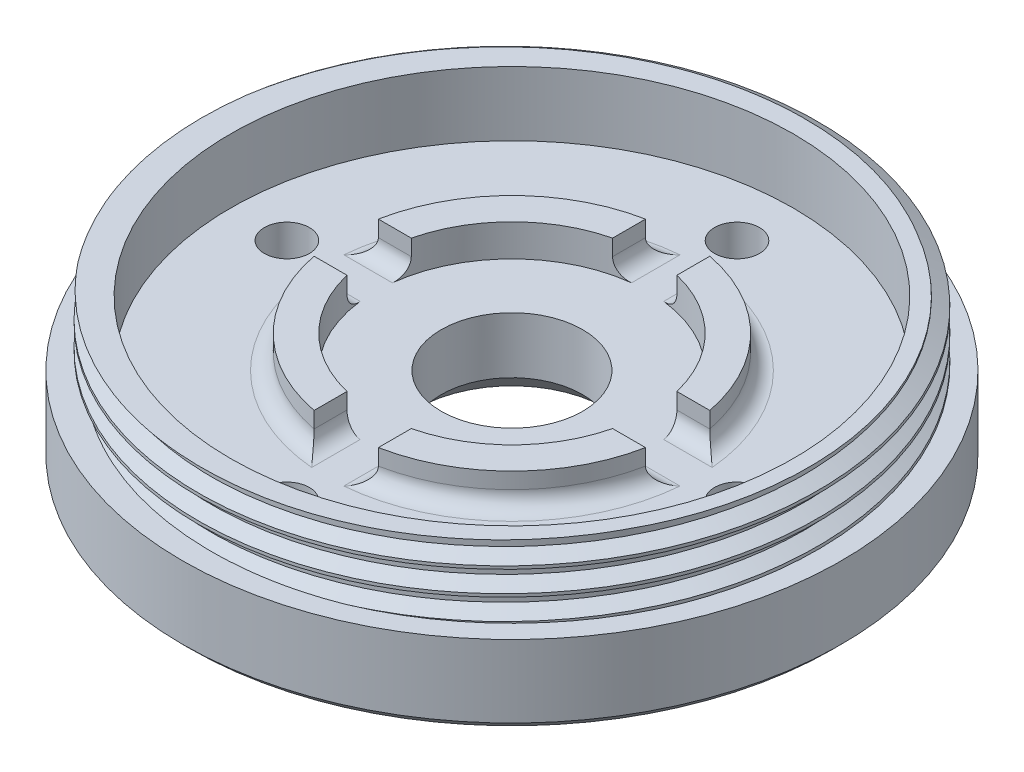
SolidWorks part; units mm, degrees
ref_plane "Front plane" through (0, 0, 0) normal (0, 0, 1) x (1, 0, 0)
ref_plane "Top plane" through (0, 0, 0) normal (0, 1, 0) x (1, 0, 0)
ref_plane "Right plane" through (0, 0, 0) normal (1, 0, 0) x (0, 0, -1)
ref_axis "Axis X" through (0, 0, 0) along (1, 0, 0)
ref_axis "Axis Y" through (0, 0, 0) along (0, 1, 0)
ref_axis "Axis Z" through (0, 0, 0) along (0, 0, 1)
sketch "Sketch1" plane through (0, 0, 0) normal (0, 1, 0) x (1, 0, 0)
  circle A0 centre (0, 0) radius 20.5
  circle A1 centre (0, 0) radius 4.4
  circle A2 centre (0, 0) radius 14 construction
  circle A3 centre (0, 14) radius 1.4
  circle A4 centre (14, 0) radius 1.4
  circle A5 centre (0, -14) radius 1.4
  circle A6 centre (-14, 0) radius 1.4
  point P16 (0, 0)
  dimension "D1" = 41
  dimension "D2" = 8.8
  dimension "D3" = 28
  dimension "D4" = 2.8
  dimension "D5" = 4
extrude "Extrude1" add sketch "Sketch1" along normal blind 5
sketch "Sketch8" plane through (0, 5, 0) normal (0, 1, 0) x (1, 0, 0)
  circle A1 centre (0, 0) radius 17.5
  circle A3 centre (0, 0) radius 18.45
  dimension "D1" = 35
  dimension "D2" = 0.95
extrude "Бобышка-Вытянуть1" add sketch "Sketch8" along normal blind 4
thread "Резьба1" pitch 1.5 method extrude trim with start face yes trim with end face yes profile "Профиль резьбы1" start angle 0, offset 2, length 0, pitch 1.5, diameter 36.9
ref_plane "Плоскость1" through (-18.45, 11, 0) normal (0, 0, 1) x (-1, 0, 0)
sketch "Профиль резьбы1" plane through (-18.45, 11, 0) normal (0, 0, 1) x (-1, 0, 0)
  line L0 (0, 0) -> (0, 1.5) construction
  line L1 (0, 0) -> (0.8119, 0.4687)
  line L2 (0.8119, 0.4687) -> (0.8119, 0.6562)
  line L3 (0.8119, 0.6562) -> (0, 1.125)
  line L4 (0.8119, 0.5625) -> (0, 0.5625) construction
  line L11 (0, 0) -> (0, 1.125)
  point P2 (0, 0)
  dimension "Pitch" = 1.5
  dimension "Profile_Angle" = 60
  dimension "Profile_Land" = 0.1875
  dimension "Profile_Height" = 0.8119
sketch "Эскиз3" plane through (0, 5, 0) normal (0, 1, 0) x (1, 0, 0)
  line L0 (0, 0) -> (0, 10) construction
  line L1 (-2, 10.3078) -> (-2, 8.2614)
  line L2 (2, 10.3078) -> (2, 8.2614)
  line L3 (10.3078, 2) -> (8.2614, 2)
  line L4 (10.3078, -2) -> (8.2614, -2)
  line L5 (2, -10.3078) -> (2, -8.2614)
  line L6 (-2, -10.3078) -> (-2, -8.2614)
  line L7 (-10.3078, -2) -> (-8.2614, -2)
  line L8 (-10.3078, 2) -> (-8.2614, 2)
  arc A0 (-2, 8.2614) -> (-8.2614, 2) centre (0, 0) ccw
  arc A1 (-2, 10.3078) -> (-10.3078, 2) centre (0, 0) ccw
  arc A2 (8.2614, 2) -> (2, 8.2614) centre (0, 0) ccw
  arc A3 (10.3078, 2) -> (2, 10.3078) centre (0, 0) ccw
  arc A4 (-8.2614, -2) -> (-2, -8.2614) centre (0, 0) ccw
  arc A5 (-10.3078, -2) -> (-2, -10.3078) centre (0, 0) ccw
  arc A6 (2, -8.2614) -> (8.2614, -2) centre (0, 0) ccw
  arc A7 (2, -10.3078) -> (10.3078, -2) centre (0, 0) ccw
  dimension "D1" = 17
  dimension "D2" = 2
  dimension "D3" = 4
  dimension "D4" = 4
extrude "Бобышка-Вытянуть2" add sketch "Эскиз3" along normal blind 2
fillet "Скругление1" radius 1 12 edges at (-2, 5, -9.2846) (2, 5, -9.2846) (7.4246, 5, -7.4246) (9.2846, 5, -2) (9.2846, 5, 2) (7.4246, 5, 7.4246) (-7.4246, 5, -7.4246) (-7.4246, 5, 7.4246) (2, 5, 9.2846) (-2, 5, 9.2846) (-9.2846, 5, 2) (-9.2846, 5, -2)
chamfer "Chamfer2" distance 1.5 angle 45 1 edges at (0, 0, 4.4)
chamfer "Chamfer3" distance 0.5 angle 45 1 edges at (0, 0, 20.5)
chamfer "Chamfer4" distance 1 angle 45 4 edges at (0, 0, -12.6) (14, 0, 1.4) (-14, 0, 1.4) (0, 0, 15.4)
equation "\"motor_D\"= 30'Motor diameter"
equation "\"motor_H\"= 13'Motor heigh"
equation "\"motor_d1\"= 25.4558'Seating diameter of screws on the fixed part of the motor"
equation "\"motor_s1\"= 2'Screws diameter on the fixed part of motor"
equation "\"motor_a2\"= 10'Seating parameter in rectangle of screws on the moving part of the motor"
equation "\"motor_s2\"= 2'Screws diameter on the moving part of motor"
equation "\"motor_Dc\"= 5'Central hole diameter of motor"
equation "\"bearing_d1\"= 6'Bearing inner diameter"
equation "\"bearing_d2\"= 17'Bearing external diameter"
equation "\"bearing h\"= 6'Bearing heigh"
equation "\"pin_d\"= 2'Pin diameter"
equation "\"pin_h\"= 12'Pin heigh"
equation "\"magnet_d1\"= 5'Magnet inner diameter"
equation "\"magnet_d2\"= 9.5'Magnet external diameter"
equation "\"magnet_h\"= 3'Magnet heigh"
equation "\"motor_b2\"= 22'Seating parameter in rectangle of screws on the moving part of the motor"
equation "\"motor_d2\"= 0'Seating diameter of screws on the moving part of the motor (if this parameter is not determine, write 0)"
equation "\"motor_cmd\"= 12'Central magnet mount diameter"
equation "\"motor_cmh\"= 1.4'Central magnet mount heigh (if not write 0)"
equation "\"motor_whR\"= 10'Distance from center of motor to wires"
equation "\"D1@Sketch1\"= IIF ( \"motor_D\" < 34 , 41 , \"motor_D\" + 8 )"
equation "\"D2@Sketch1\"=\"ft_sensor_d1\"-1"
equation "\"D4@Sketch1\"=3-\"print_offset\""
equation "\"print_offset\"= 0.2'Offset for printing holes"
equation "\"ft_sensor_d1\"= 9.8"
equation "\"ft_sensor_d2\"= 24.9"
equation "\"ft_sensor_d3\"= 22.6'Inner diameter of "
equation "\"ft_sensor_h\"= 7.1"
equation "\"ft_sensor_whD\" = 5"
equation "\"D1@Sketch8\" = IIF ( \"motor_D\" < 34 , 41 , \"motor_D\" + 8 ) - 6"
equation "\"D2@Sketch8\"= 0.95"
equation "\"D1@Эскиз3\"=\"bearing_d2\""
equation "\"D1@Бобышка-Вытянуть2\"=\"bearing h\"/3"
